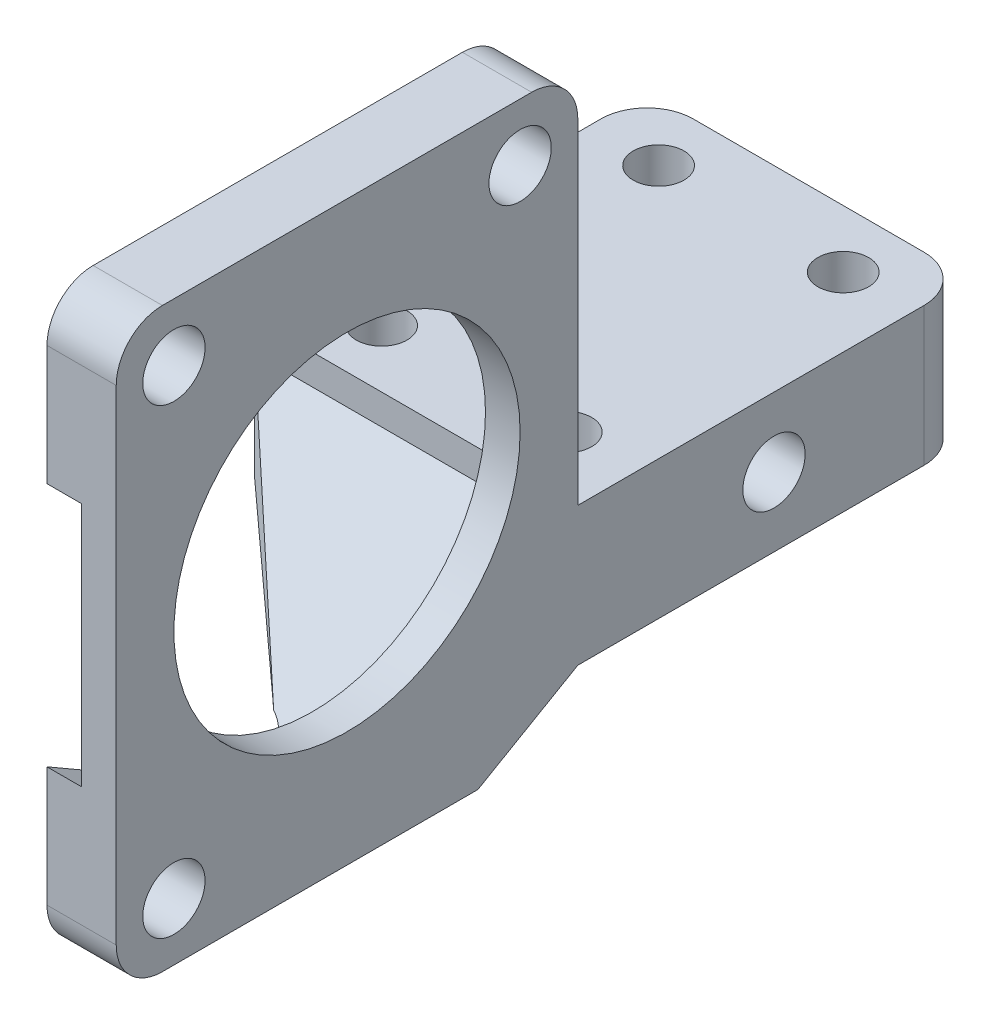
SolidWorks part; units mm, degrees
material "PLA"
ref_plane "前视基准面" through (0, 0, 0) normal (0, 0, 1) x (1, 0, 0)
ref_plane "上视基准面" through (0, 0, 0) normal (0, 1, 0) x (1, 0, 0)
ref_plane "右视基准面" through (0, 0, 0) normal (1, 0, 0) x (0, 0, -1)
sketch "草图1" plane through (0, 0, 0) normal (0, 1, 0) x (1, 0, 0)
  line L1 (-7, -8.5) -> (7, -8.5)
  line L2 (-7, -8.5) -> (-7, 8.5)
  line L3 (-7, 8.5) -> (7, 8.5)
  line L4 (7, -8.5) -> (7, 8.5)
  line L5 (0, 8.5) -> (0, -8.5) construction
  line L6 (-7, 0) -> (7, 0) construction
  line L8 (7, 8.5) -> (7, -8.5) construction
  circle A0 centre (-4, 6) radius 1.1
  circle A1 centre (4, 6) radius 1.1
  circle A2 centre (4, -6) radius 1.1
  circle A3 centre (-4, -6) radius 1.1
  point P0 (0, 0)
  dimension "D5" = 2.2
  dimension "D1" = 8
  dimension "D2" = 12
  dimension "D3" = 17
  dimension "D4" = 14
extrude "凸台-拉伸1" add sketch "草图1" along normal blind 6
sketch "草图10" plane through (7, 0, 0) normal (1, 0, 0) x (0, 0, -1)
  line L0 (-8.5, 6) -> (-8.5, 0) construction
  line L1 (-28.5, -2.5) -> (-8.5, -2.5)
  line L2 (-28.5, -2.5) -> (-28.5, 22.5)
  line L3 (-28.5, 22.5) -> (-8.5, 22.5)
  line L4 (-8.5, -2.5) -> (-8.5, 22.5)
  line L5 (-18.5, 22.5) -> (-18.5, -2.5) construction
  line L6 (-28.5, 10) -> (-8.5, 10) construction
  line L7 (8.5, 6) -> (-8.5, 6) construction
  circle A0 centre (-18.5, 10) radius 7.5
  circle A1 centre (-18.5, 10) radius 11 construction
  circle A2 centre (-26, 20) radius 1.35
  circle A3 centre (-11, 20) radius 1.35
  circle A4 centre (-11, 0) radius 1.35 construction
  circle A5 centre (-26, 0) radius 1.35
  point P0 (-18.5, 10)
  dimension "D1" = 15
  dimension "D5" = 22
  dimension "D6" = 2.7
  dimension "D2" = 20
  dimension "D3" = 25
  dimension "D4" = 4
  dimension "D7" = 15
  dimension "D8" = 20
extrude "凸台-拉伸8" add sketch "草图10" against normal blind 3
sketch "草图11" plane through (7, 0, 0) normal (1, 0, 0) x (0, 0, -1)
  line L0 (8.5, 3) -> (-8.5, 3) construction
  line L2 (0, 0) -> (0, 3) construction
  line L4 (8.5, 6) -> (8.5, 0) construction
  line L5 (-8.5, 0) -> (-8.5, 6) construction
  circle A1 centre (0, 3) radius 1.35
  dimension "D1" = 2.7
extrude "切除-拉伸1" cut sketch "草图11" against normal through all
sketch "草图14" plane through (0, 0, 0) normal (0, -1, 0) x (1, 0, 0)
  line L0 (-7, 8.5) -> (4, 18.5)
  line L1 (4, 28.5) -> (4, 8.5) construction
  line L2 (4, 18.5) -> (4, 8.5)
  line L3 (4, 8.5) -> (-7, 8.5)
  dimension "D1" = 10
extrude "凸台-拉伸9" add sketch "草图14" against normal up to surface (6 mm away) up to face at (0.8, 6, 1.7)
sketch "草图12" plane through (4, 0, 0) normal (-1, 0, 0) x (0, 0, 1)
  line L0 (8.9, 15.5426) -> (8.5, 15.3116)
  line L1 (18.5, 21.0851) -> (8.9, 15.5426)
  line L2 (8.9, 15.5426) -> (8.9, 4.4574) construction
  line L3 (8.9, 4.4574) -> (18.5, -1.0851)
  line L4 (18.5, -1.0851) -> (28.1, 4.4574)
  line L5 (28.1, 4.4574) -> (28.1, 15.5426) construction
  line L6 (28.1, 15.5426) -> (18.5, 21.0851)
  line L7 (8.5, 6) -> (8.5, 22.5) construction
  line L8 (8.5, 15.3116) -> (8.5, 4.6884)
  line L9 (8.5, 6) -> (8.5, 0) construction
  line L10 (8.5, 4.6884) -> (8.9, 4.4574)
  line L11 (18.5, 10) -> (18.5, 21.0851) construction
  line L12 (28.5, 4.6884) -> (28.1, 4.4574)
  line L13 (28.5, 15.3116) -> (28.5, 4.6884)
  line L14 (28.1, 15.5426) -> (28.5, 15.3116)
  circle A0 centre (18.5, 10) radius 9.6 construction
  dimension "D1" = 19.2
extrude "切除-拉伸2" cut sketch "草图12" against normal blind 1.5 and the other way through all
sketch "草图15" plane through (4, 0, 0) normal (-1, 0, 0) x (0, 0, 1)
  line L0 (8.5, 0) -> (8.5, -2.5)
  line L1 (8.5, -2.5) -> (12.8301, -2.5)
  line L2 (28.5, -2.5) -> (8.5, -2.5) construction
  line L3 (12.8301, -2.5) -> (8.5, 0)
  line L4 (8.5, 4.6884) -> (18.5, -1.0851) construction
extrude "切除-拉伸3" cut sketch "草图15" against normal through all
fillet "圆角1" radius 2 5 edges at (5.5, -2.5, 28.5) (5.5, 22.5, 28.5) (5.5, 22.5, 8.5) (7, 3, -8.5) (-7, 3, -8.5)
fillet "圆角2" radius 2.5 1 edges at (4, 0, 12.5603)
